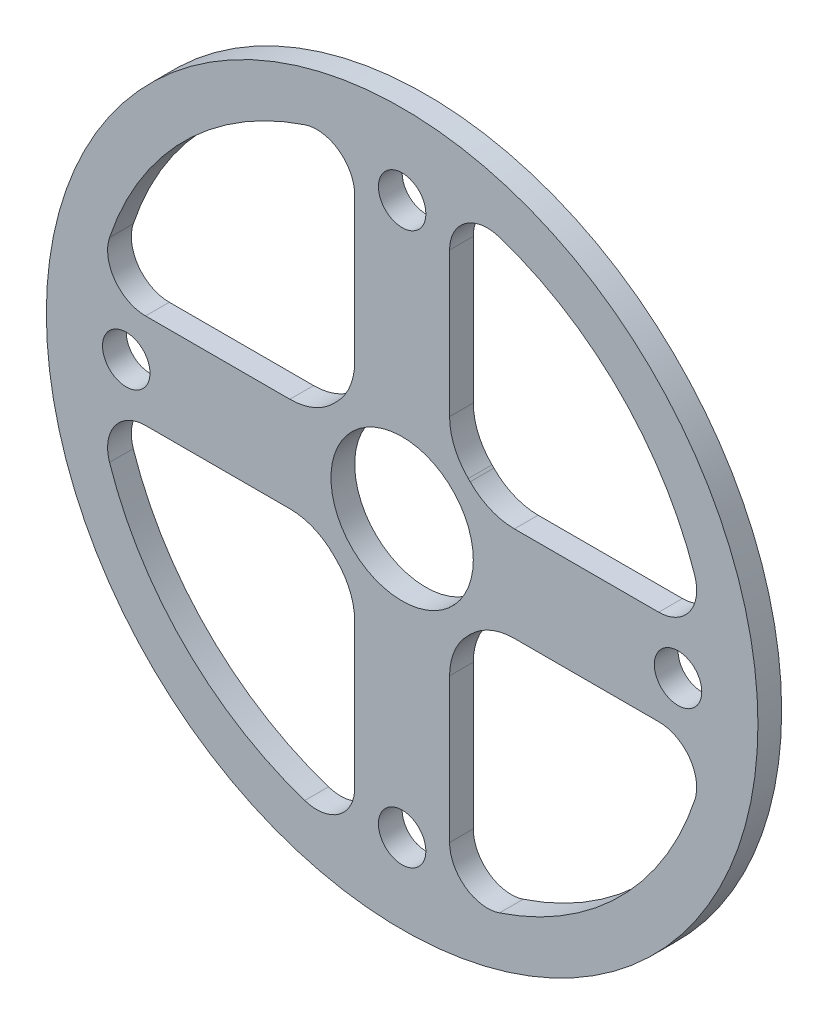
SolidWorks part; units mm, degrees
ref_plane "Front Plane" through (0, 0, 0) normal (0, 0, 1) x (1, 0, 0)
ref_plane "Top Plane" through (0, 0, 0) normal (0, 1, 0) x (1, 0, 0)
ref_plane "Right Plane" through (0, 0, 0) normal (1, 0, 0) x (0, 0, -1)
sketch "Sketch1" plane through (0, 0, 0) normal (0, 0, 1) x (1, 0, 0)
  circle A0 centre (0, 0) radius 75
  circle A1 centre (0, 0) radius 15
  dimension "D1" = 150
  dimension "D2" = 30
extrude "Boss-Extrude1" add sketch "Sketch1" along normal blind 5
sketch "Sketch2" plane through (0, 0, 5) normal (0, 0, 1) x (1, 0, 0)
  line L0 (0, 0) -> (0, -75) construction
  line L1 (0, 0) -> (75, 0) construction
  line L2 (10, -10) -> (10, -11.1803)
  line L3 (10, -10) -> (11.1803, -10)
  line L4 (-10, -10) -> (-10, -64.2262)
  line L5 (-10, -10) -> (-64.2262, -10)
  line L6 (-10, 10) -> (-64.2262, 10)
  line L7 (-10, 10) -> (-10, 64.2262)
  line L8 (10, 10) -> (10, 64.2262)
  line L9 (10, 10) -> (64.2262, 10)
  line L10 (10, -17.3205) -> (10, -64.2262)
  line L11 (17.3205, -10) -> (64.2262, -10)
  line L12 (-10, -17.3205) -> (-10, -64.2262)
  line L13 (-17.3205, -10) -> (-64.2262, -10)
  line L14 (-17.3205, 10) -> (-64.2262, 10)
  line L15 (-10, 17.3205) -> (-10, 64.2262)
  line L16 (10, 17.3205) -> (10, 64.2262)
  line L17 (17.3205, 10) -> (64.2262, 10)
  circle A0 centre (58.1568, 0) radius 5
  circle A1 centre (0, -58.1568) radius 5
  circle A2 centre (-58.1568, 0) radius 5
  circle A3 centre (0, 58.1568) radius 5
  circle A4 centre (0, 0) radius 75 construction
  arc A5 (0, -75) -> (75, 0) centre (0, 0) ccw construction
  arc A6 (10, -11.1803) -> (11.1803, -10) centre (0, 0) ccw
  circle A7 centre (0, 0) radius 15 construction
  arc A8 (10, -64.2262) -> (64.2262, -10) centre (0, 0) ccw
  arc A9 (-64.2262, -10) -> (-10, -64.2262) centre (0, 0) ccw
  arc A10 (-10, 64.2262) -> (-64.2262, 10) centre (0, 0) ccw
  arc A11 (64.2262, 10) -> (10, 64.2262) centre (0, 0) ccw
  arc A12 (17.3205, -10) -> (10, -17.3205) centre (0, 0) cw
  arc A13 (-64.2262, -10) -> (-10, -64.2262) centre (0, 0) ccw
  arc A14 (-10, -17.3205) -> (-17.3205, -10) centre (0, 0) cw
  arc A15 (-10, 64.2262) -> (-64.2262, 10) centre (0, 0) ccw
  arc A16 (-17.3205, 10) -> (-10, 17.3205) centre (0, 0) cw
  arc A17 (64.2262, 10) -> (10, 64.2262) centre (0, 0) ccw
  arc A18 (10, 17.3205) -> (17.3205, 10) centre (0, 0) cw
  point P11 (0, 0)
  point P36 (0, 0)
  point P51 (0, 0)
  circle M12 centre (0, 0) radius 15
  dimension "D1" = 10
  dimension "D5" = 65
  dimension "D7" = 20
  dimension "D3" = 10
  dimension "D4" = 10
  dimension "D2" = 4
  dimension "D6" = 4
  dimension "D8" = 4
extrude "Cut-Extrude1" cut sketch "Sketch2" against normal blind 5 contours L7 A10 L6 M12 | L5 A9 L4 M12 | L9 A11 L8 M12 | A1 | A2 | A0 | A3 | L3 A8 L2 region at (-32.2447, -32.2447, 5) region at (32.2447, 32.2447, 5) region at (-32.2447, 32.2447, 5) region at (58.1568, 0, 5) region at (0, -58.1568, 5) region at (-58.1568, 0, 5) region at (0, 58.1568, 5)
extrude "Cut-Extrude2" cut sketch "Sketch2<3>" against normal blind 5 contours L11 A12 L10 A8 region at (32.2447, -32.2447, 5)
sketch "Sketch2<3>" plane through (0, 0, 5) normal (0, 0, 1) x (1, 0, 0) same geometry as "Sketch2"
fillet "Fillet1" radius 13 8 edges at (10, -17.3205, 2.5) (17.3205, -10, 2.5) (17.3205, 10, 2.5) (10, 17.3205, 2.5) (-10, 17.3205, 2.5) (-17.3205, 10, 2.5) (-10, -17.3205, 2.5) (-17.3205, -10, 2.5)
fillet "Fillet2" radius 8 8 edges at (-64.2262, -10, 2.5) (-10, -64.2262, 2.5) (-64.2262, 10, 2.5) (10, -64.2262, 2.5) (64.2262, -10, 2.5) (-10, 64.2262, 2.5) (10, 64.2262, 2.5) (64.2262, 10, 2.5)
